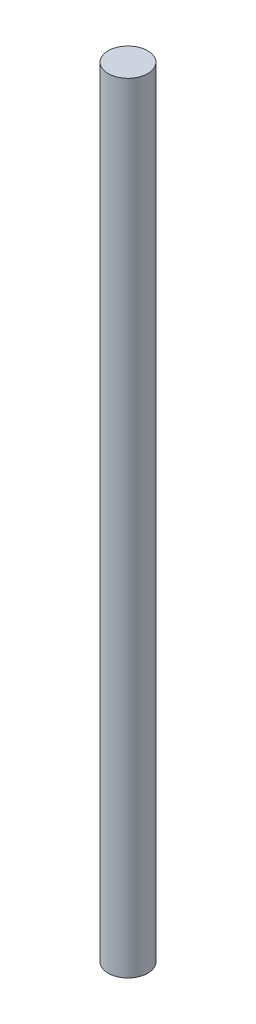
SolidWorks part; units mm, degrees
ref_plane "Front Plane" through (0, 0, 0) normal (0, 0, 1) x (1, 0, 0)
ref_plane "Top Plane" through (0, 0, 0) normal (0, 1, 0) x (1, 0, 0)
ref_plane "Right Plane" through (0, 0, 0) normal (1, 0, 0) x (0, 0, -1)
sketch "Sketch1" plane through (0, 0, 0) normal (0, 1, 0) x (1, 0, 0)
  circle A0 centre (0, 0) radius 12.7
  dimension "D1" = 25.4
extrude "Boss-Extrude1" add sketch "Sketch1" along normal blind 500
equation "\"carbon_fiber_tube_diam\"= 1in"
equation "\"clip_tube_diam\"= 6mm"
equation "\"D1@Sketch1\"=\"carbon_fiber_tube_diam\""
equation "\"middle_tube_len\"= 500mm"
equation "\"D1@Boss-Extrude1\"=\"middle_tube_len\""
